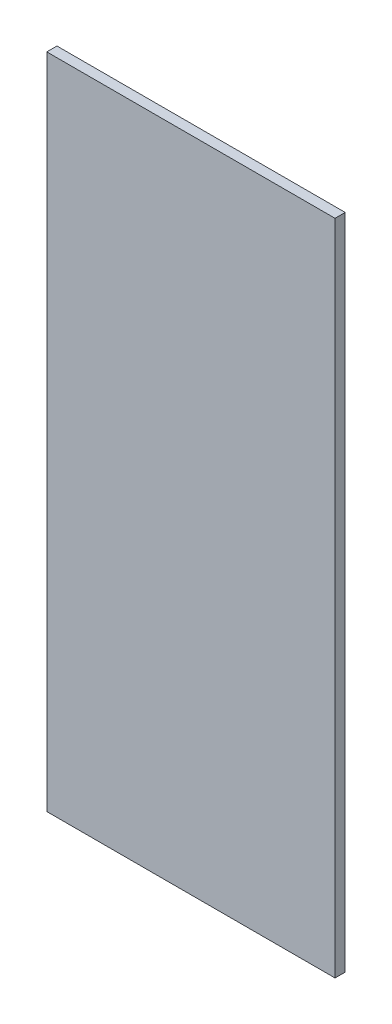
SolidWorks part; units mm, degrees
material "PET"
ref_plane "Front Plane" through (0, 0, 0) normal (0, 0, 1) x (1, 0, 0)
ref_plane "Top Plane" through (0, 0, 0) normal (0, 1, 0) x (1, 0, 0)
ref_plane "Right Plane" through (0, 0, 0) normal (1, 0, 0) x (0, 0, -1)
sketch "Sketch1" plane through (0, 0, 0) normal (0, 0, 1) x (1, 0, 0)
  line L1 (-28.5714, 365.1048) -> (141.4286, 365.1048)
  line L2 (-28.5714, 365.1048) -> (-28.5714, -22.8952)
  line L3 (-28.5714, -22.8952) -> (141.4286, -22.8952)
  line L4 (141.4286, 365.1048) -> (141.4286, -22.8952)
  dimension "D1" = 388
  dimension "D2" = 170
extrude "Boss-Extrude1" add sketch "Sketch1" along normal blind 6
